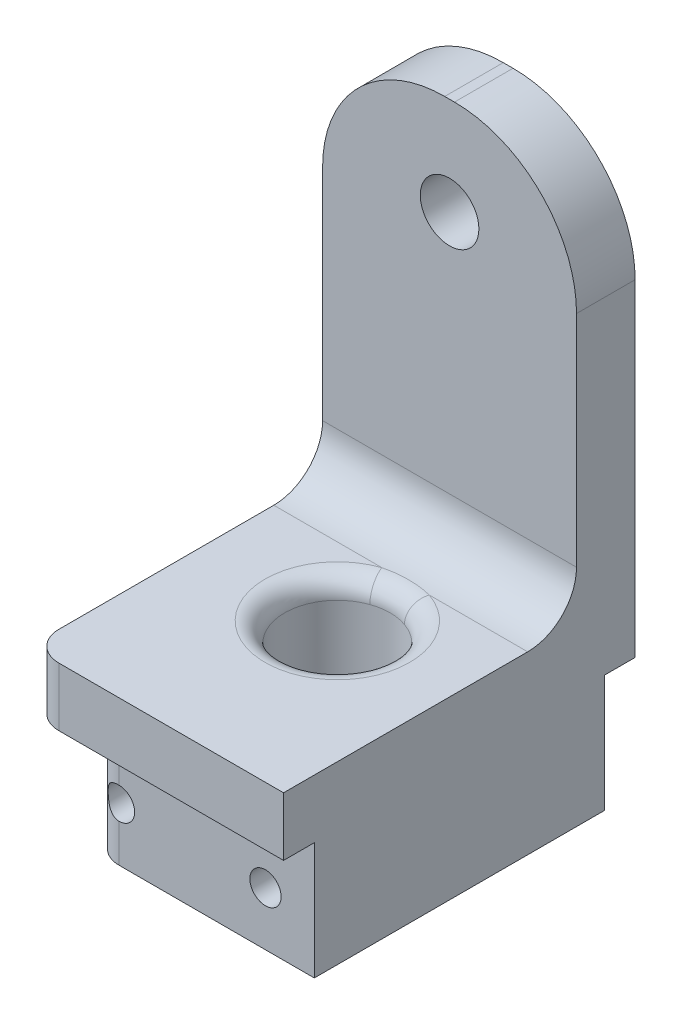
SolidWorks part; units mm, degrees
ref_plane "Front Plane" through (0, 0, 0) normal (0, 0, 1) x (1, 0, 0)
ref_plane "Top Plane" through (0, 0, 0) normal (0, 1, 0) x (1, 0, 0)
ref_plane "Right Plane" through (0, 0, 0) normal (1, 0, 0) x (0, 0, -1)
sketch "Sketch1" plane through (0, -44, 0) normal (0, 1, 0) x (1, 0, 0)
  line L0 (50.2641, 25) -> (50.2641, 28) construction
  line L1 (50.2641, -8) -> (50.2641, 28)
  line L2 (50.2641, -8) -> (27.2641, -8) construction
  line L3 (50.2641, -8) -> (27.2641, -8)
  line L4 (24.2641, -5) -> (24.2641, 25)
  line L5 (27.2641, 28) -> (50.2641, 28)
  arc A0 (27.2641, 28) -> (24.2641, 25) centre (27.2641, 25) ccw construction
  arc A1 (24.2641, -5) -> (27.2641, -8) centre (27.2641, -5) ccw construction
  arc A2 (27.2641, 28) -> (24.2641, 25) centre (27.2641, 25) ccw
  arc A3 (24.2641, -5) -> (27.2641, -8) centre (27.2641, -5) ccw
extrude "Boss-Extrude1" add sketch "Sketch1" along normal blind 6
sketch "Sketch2" plane through (0, -38, 0) normal (0, 1, 0) x (1, 0, 0)
  line L0 (24.2641, 25) -> (24.2641, -5) construction
  line L1 (50.2641, 28) -> (24.2641, 28)
  line L2 (50.2641, 28) -> (50.2641, 22)
  line L3 (50.2641, 22) -> (24.2641, 22)
  line L4 (24.2641, 28) -> (24.2641, 22)
  dimension "D1" = 6
extrude "Boss-Extrude2" add sketch "Sketch2" along normal blind 40
fillet "Fillet1" radius 12.5 2 edges at (24.2641, 2, -25) (50.2641, 2, -25)
sketch "Sketch3" plane through (0, 0, -22) normal (0, 0, 1) x (1, 0, 0)
  circle A0 centre (37.2641, -8) radius 3
extrude "Cut-Extrude1" cut sketch "Sketch3" against normal through all
sketch "Sketch4" plane through (0, -44, 0) normal (0, -1, 0) x (1, 0, 0)
  line L3 (50.2641, 4.85) -> (50.2641, -24.85)
  line L6 (50.2641, -24.85) -> (30.2641, -24.85)
  line L7 (27.4141, 2) -> (27.4141, -22)
  line L8 (30.2641, 4.85) -> (50.2641, 4.85)
  arc A4 (27.4141, -22) -> (30.2641, -24.85) centre (30.2641, -22) ccw
  arc A5 (30.2641, 4.85) -> (27.4141, 2) centre (30.2641, 2) ccw
extrude "Boss-Extrude3" add sketch "Sketch4" along normal blind 12
fillet "Fillet2" radius 5 1 edges at (37.2641, -38, -22)
sketch "Sketch5" plane through (0, 0, -24.85) normal (0, 0, -1) x (-1, 0, 0)
  circle A0 centre (-45.2641, -50.5) radius 1.6
  circle A1 centre (-30.2641, -50.5) radius 1.6
extrude "Cut-Extrude2" cut sketch "Sketch5" against normal through all
sketch "Sketch6" plane through (0, -38, 0) normal (0, -1, 0) x (1, 0, 0)
  line L2 (24.2641, -28) -> (27.2641, -28)
  line L3 (24.2641, -25) -> (24.2641, -28)
  line L4 (24.2641, -28) -> (27.2641, -28)
  line L5 (24.2641, -25) -> (24.2641, -28)
  arc A1 (24.2641, -25) -> (27.2641, -28) centre (27.2641, -25) ccw
  arc A2 (24.2641, -25) -> (27.2641, -28) centre (27.2641, -25) ccw
  dimension "D1" = 0
extrude "Cut-Extrude3" cut sketch "Sketch6" against normal through all
sketch "Sketch7" plane through (0, -56, 0) normal (0, -1, 0) x (1, 0, 0)
  line L0 (31.8641, 4.85) -> (30.2641, 4.85) construction
  line L1 (46.8641, 4.85) -> (43.6641, 4.85) construction
  line L2 (31.8641, 4.85) -> (30.2641, 4.85) construction
  line L3 (46.8641, 4.85) -> (43.6641, 4.85) construction
  line L4 (30.2641, 4.85) -> (30.2641, -10.0084) construction
  line L5 (45.2641, 4.85) -> (45.2641, -10.0084) construction
  line L6 (30.2641, -10.0084) -> (45.2641, -10.0084) construction
  circle A0 centre (37.7641, -10.0084) radius 5.4
extrude "Cut-Extrude4" cut sketch "Sketch7" against normal up to surface (18 mm away) up to face at (35.1398, -38, -2.4757)
fillet "Fillet3" radius 2 2 edges at (43.1641, -56, -10.0084) (32.3641, -38, -10.0084)
